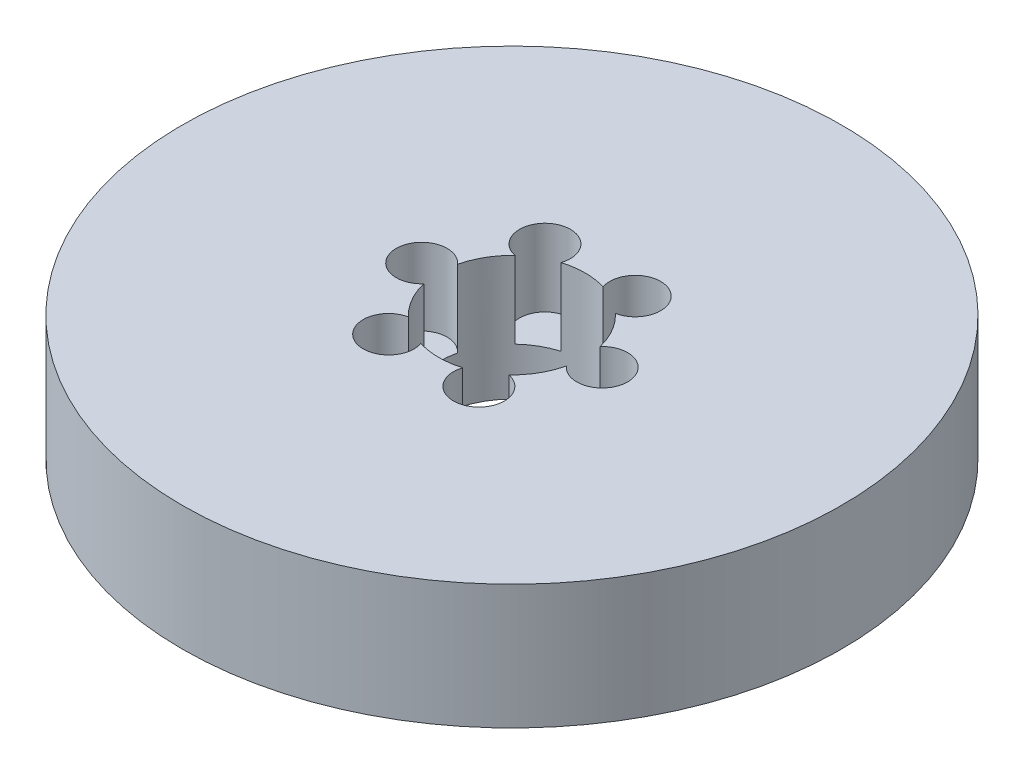
SolidWorks part; units mm, degrees
ref_plane "Front Plane" through (0, 0, 0) normal (0, 0, 1) x (1, 0, 0)
ref_plane "Top Plane" through (0, 0, 0) normal (0, 1, 0) x (1, 0, 0)
ref_plane "Right Plane" through (0, 0, 0) normal (1, 0, 0) x (0, 0, -1)
sketch "Sketch1" plane through (0, 0, 0) normal (0, 1, 0) x (1, 0, 0)
  circle A0 centre (0, 0) radius 45
  dimension "FLANGE_OD" = 90
extrude "Boss-Extrude1" add sketch "Sketch1" along normal blind 17
sketch "Sketch2" plane through (0, 0, 0) normal (0, 1, 0) x (1, 0, 0)
  circle A0 centre (0, 0) radius 10
  dimension "BORE_D" = 20
extrude "Cut-Extrude1" cut sketch "Sketch2" along normal through all
sketch "Sketch3" plane through (0, 17, 0) normal (0, 1, 0) x (1, 0, 0)
  circle A0 centre (0, 0) radius 12.3237 construction
  circle A1 centre (-12.3237, 0) radius 3.4739
  dimension "BOLT_D" = 6.9478
  dimension "BOLT_PCD" = 24.6473
extrude "Cut-Extrude2" cut sketch "Sketch3" against normal blind 10.494
pattern_circular "CirPattern1" count 6 over 360 about axis through (0, 0, 0) along (0, 1, 0) of "Cut-Extrude2"
